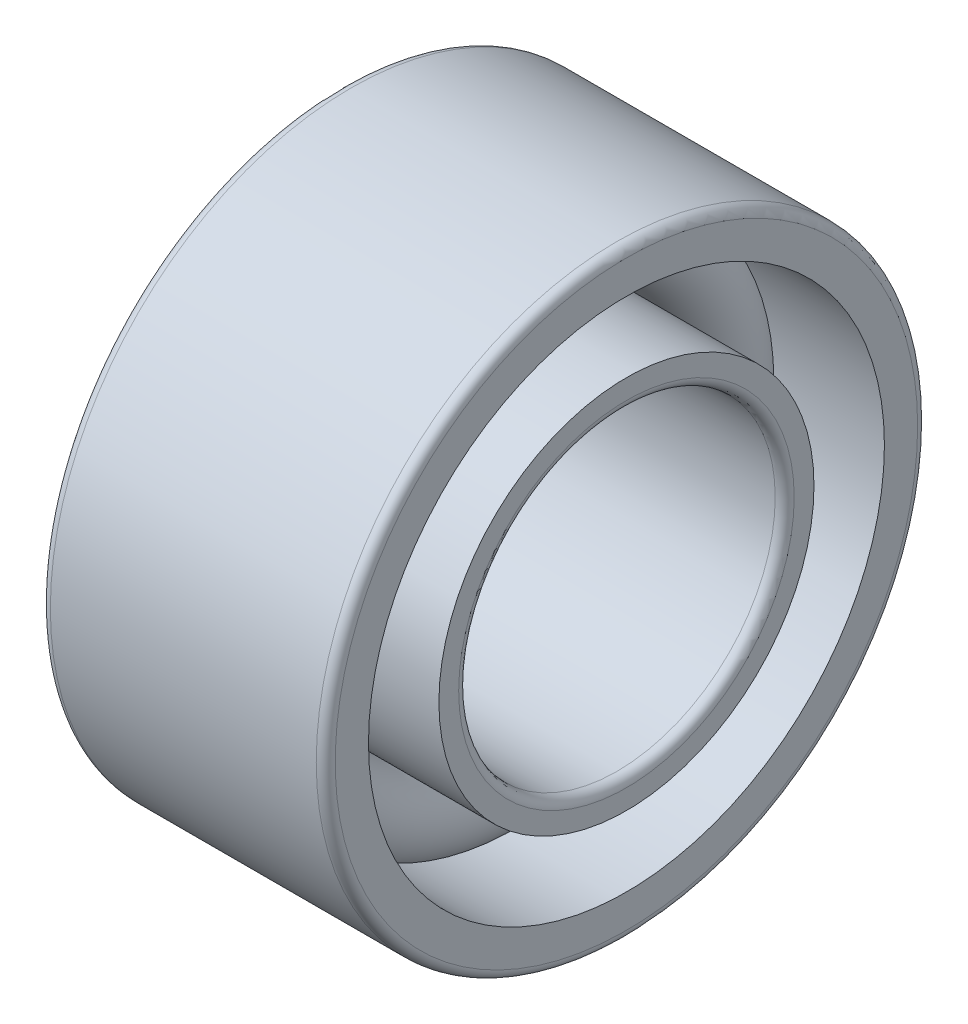
SolidWorks part; units mm, degrees
ref_plane "Plane1" through (0, 0, 0) normal (0, 0, 1) x (1, 0, 0)
ref_plane "Plane2" through (0, 0, 0) normal (0, 1, 0) x (1, 0, 0)
ref_plane "Plane3" through (0, 0, 0) normal (1, 0, 0) x (0, 0, -1)
other "Configuration Table"
sketch "Clipboard" plane through (0, 0, 0) normal (0, 0, 1) x (1, 0, 0)
  line L0 (-10, 0) -> (10, 0) construction
  line L1 (0, 0) -> (22.3471, -0.7804)
  line L2 (0, 0) -> (7.2456, 0.253)
  line L3 (0, 0) -> (22.3471, -0.7804)
  line L4 (0, 0) -> (-22.3573, -0.3902)
  dimension "BallCLRad" = 7.25
sketch "CagSpiSke" plane through (0, 0, 0) normal (0, 0, 1) x (1, 0, 0)
  line L0 (0.3375, 7.025) -> (0.3375, 7.475)
  line L1 (0.3375, 7.475) -> (-0.3375, 7.475)
  line L2 (-0.3375, 7.475) -> (-0.3375, 7.025)
  line L3 (-0.3375, 7.025) -> (0.3375, 7.025)
  line L4 (-20.6375, 0) -> (20.6375, 0) construction
  line L5 (0, 0) -> (0, 23.7692) construction
  dimension "OD" = 14.95
  dimension "ID" = 14.05
revolve "CageSpine" add sketch "CagSpiSke" angle 0.001 about L4
ref_axis "Axis1" through (-50, 0, 0) along (1, 0, 0)
sketch "CagBalSke" plane through (0, 0, 0) normal (0, 0, 1) x (1, 0, 0)
  line L0 (-1.485, 7.25) -> (1.485, 7.25)
  line L1 (-1.905, 7.25) -> (1.905, 7.25) construction
  line L2 (-10, 0) -> (10, 0) construction
  line L3 (0, 0) -> (0, 24) construction
  arc A0 (1.485, 7.25) -> (-1.485, 7.25) centre (0, 7.25) cw
  dimension "BallCLRad" = 7.25
revolve "CageBall" [suppressed] add sketch "CagBalSke" angle 360 about L1 reverse direction yes
pattern_circular "CageBalls" [suppressed] count 2 every 180 about axis through (-50, 0, 0) along (1, 0, 0)
sketch "CagTrmODSke" plane through (0, 0, 0) normal (0, 0, 1) x (1, 0, 0)
  line L0 (1.486, 7.475) -> (1.486, 8.736)
  line L1 (1.486, 8.736) -> (-1.486, 8.736)
  line L2 (-1.486, 8.736) -> (-1.486, 7.475)
  line L3 (-1.486, 7.475) -> (1.486, 7.475)
  line L4 (-20.6375, 0) -> (20.6375, 0) construction
  line L5 (0, 0) -> (0, 25) construction
  dimension "Width" = 2.972
  dimension "ID" = 14.95
  dimension "OD" = 17.472
revolve "CageTrimOD" [suppressed] cut sketch "CagTrmODSke" angle 360 about L4 reverse direction yes
sketch "CagTrmIDSke" plane through (0, 0, 0) normal (0, 0, 1) x (1, 0, 0)
  line L0 (1.486, 5.766) -> (1.486, 7.025)
  line L1 (1.486, 7.025) -> (-1.486, 7.025)
  line L2 (-1.486, 7.025) -> (-1.486, 5.766)
  line L3 (-1.486, 5.766) -> (1.486, 5.766)
  line L4 (-20.6375, 0) -> (20.6375, 0) construction
  line L5 (0, 0) -> (0, 25) construction
  dimension "Width" = 2.972
  dimension "ID" = 11.532
  dimension "OD" = 14.05
revolve "CageTrimID" [suppressed] cut sketch "CagTrmIDSke" angle 360 about L4 reverse direction yes
sketch "BalSimSke" plane through (0, 0, 0) normal (0, 0, 1) x (1, 0, 0)
  line L0 (-10, 0) -> (10, 0) construction
  line L1 (-10, 7.25) -> (10, 7.25) construction
  line L2 (0, 0) -> (0, 23) construction
  circle A0 centre (0, 7.25) radius 1.35
  dimension "BallCLRad" = 7.25
  dimension "Ball_diameter" = 2.7
revolve "BallsSimplified" add sketch "BalSimSke" angle 360 about L0
sketch "BalDetSke" plane through (0, 0, 0) normal (0, 0, 1) x (1, 0, 0)
  line L0 (-1.35, 7.25) -> (1.35, 7.25)
  line L1 (-1.905, 7.25) -> (1.905, 7.25) construction
  line L2 (0, 0) -> (0, 25) construction
  arc A0 (1.35, 7.25) -> (-1.35, 7.25) centre (0, 7.25) cw
  dimension "BallCLRad" = 7.25
  dimension "Ball_diameter" = 2.7
revolve "BallDetailed" [suppressed] add sketch "BalDetSke" angle 360 about L1 reverse direction yes
sketch "InnRacSke" plane through (0, 0, 0) normal (0, 0, 1) x (1, 0, 0)
  line L0 (-0.9724, 6.35) -> (-4.5, 6.35)
  line L1 (-4.5, 6.35) -> (-4.5, 5.3)
  line L2 (-4.2, 5) -> (4.2, 5)
  line L3 (4.5, 5.3) -> (4.5, 5.925)
  line L4 (0, 5.925) -> (4.5, 5.925)
  line L5 (-20.6375, 0) -> (20.6375, 0) construction
  line L6 (0, 0) -> (0, 30) construction
  arc A0 (-4.5, 5.3) -> (-4.2, 5) centre (-4.2, 5.3) ccw
  arc A1 (4.2, 5) -> (4.5, 5.3) centre (4.2, 5.3) ccw
  arc A2 (0, 5.925) -> (-0.9724, 6.35) centre (0, 7.25) cw
  dimension "BallCLRad" = 7.25
  dimension "Fillet_radius" = 0.3
  dimension "Ball_diameter" = 2.65
  dimension "ID" = 10
  dimension "OD" = 12.7
  dimension "Width" = 9
revolve "InnerRace" add sketch "InnRacSke" angle 360 about L5 reverse direction yes
sketch "OutRacSke" plane through (0, 0, 0) normal (0, 0, 1) x (1, 0, 0)
  line L0 (0, 8.575) -> (-4.5, 8.575)
  line L1 (-4.5, 8.575) -> (-4.5, 9.2)
  line L2 (-4.2, 9.5) -> (4.2, 9.5)
  line L3 (4.5, 9.2) -> (4.5, 8.15)
  line L4 (4.5, 8.15) -> (0.9724, 8.15)
  line L5 (-20.6375, 0) -> (20.6375, 0) construction
  line L6 (0, 0) -> (0, 30) construction
  arc A0 (-4.5, 9.2) -> (-4.2, 9.5) centre (-4.2, 9.2) cw
  arc A1 (4.2, 9.5) -> (4.5, 9.2) centre (4.2, 9.2) cw
  arc A2 (0.9724, 8.15) -> (0, 8.575) centre (0, 7.25) ccw
  dimension "BallCLRad" = 7.25
  dimension "Fillet_radius" = 0.3
  dimension "Ball_diameter" = 2.65
  dimension "Width" = 9
revolve "OuterRace" add sketch "OutRacSke" angle 360 about L5 reverse direction yes
pattern_circular "BallsDetailed" [suppressed] count 2 every 180 about axis through (-50, 0, 0) along (1, 0, 0)
equation "\"BallCLRad@Clipboard\" = ( \"OD@OutRacSke\" + \"ID@InnRacSke\" ) / 4"
equation "\"BallCLRad@BalSimSke\" = \"BallCLRad@Clipboard\""
equation "\"BallCLRad@BalDetSke\" = \"BallCLRad@Clipboard\""
equation "\"BallCLRad@InnRacSke\" = \"BallCLRad@Clipboard\""
equation "\"BallCLRad@OutRacSke\" = \"BallCLRad@Clipboard\""
equation "\"Ball_diameter@InnRacSke\" = \"Ball_diameter@BalDetSke\" - 0.05"
equation "\"Ball_diameter@OutRacSke\" = \"Ball_diameter@BalDetSke\" - 0.05"
equation "\"Ball_diameter@BalSimSke\" = \"Ball_diameter@BalDetSke\""
equation "\"Width@OutRacSke\" = \"Width@InnRacSke\""
equation "\"Fillet_radius@OutRacSke\" = \"Fillet_radius@InnRacSke\""
equation "\"Max_count@Clipboard\" = int( 3.14159265 / atn(( \"Ball_diameter@BalDetSke\" / 2) / sqr( \"BallCLRad@Clipboard\"  *  \"BallCLRad@Clipboard\" - ( \"Ball_diameter@BalDetSke\" / 2) *  ( \"Ball_diameter@BalDetSke\" / 2))))"
equation "\"Max_count@Clipboard\" = ((sgn( \"Max_count@Clipboard\" - \"Count@Clipboard\" )-1)*( \"Max_count@Clipboard\" - \"Count@Clipboard\" ))/-2+ \"Count@Clipboard\""
equation "\"Count@BallsDetailed\" = int( \"Show_count@Clipboard\" ) "
equation "\"Count@BallsDetailed\" = ((sgn( \"Count@BallsDetailed\" - \"Max_count@Clipboard\" )-1)*( \"Count@BallsDetailed\" - \"Max_count@Clipboard\" ))/-2+ \"Max_count@Clipboard\""
equation "\"Count@BallsDetailed\" = ((sgn( \"Count@BallsDetailed\" - \"Min_count@Clipboard\" )+1)*( \"Count@BallsDetailed\" - \"Min_count@Clipboard\"))/2 +\"Min_count@Clipboard\""
equation "\"Angle@BallsDetailed\" = 360.0 / \"Max_count@Clipboard\""
equation "\"BallCLRad@CagBalSke\" = \"BallCLRad@Clipboard\""
equation "\"Count@CageBalls\" = \"Count@BallsDetailed\""
equation "\"Angle@CageBalls\" = \"Angle@BallsDetailed\""
equation "\"Angle@CageSpine\" =  \"Angle@CageBalls\" * ( \"Count@CageBalls\" -1 + int( \"Count@CageBalls\" / \"Max_count@Clipboard\" ) )  + 0.001 -  int( \"Count@CageBalls\" / \"Max_count@Clipboard\" ) * 0.001"
equation "\"Angle@CageSpine\" =  \"Angle@CageSpine\" * int( \"Min_count@Clipboard\" / 2) + int(1 / \"Min_count@Clipboard\")  * 0.001"
equation "\"CageWallOD@CagBalSke\" =  \"Ball_diameter@BalDetSke\" * 1.1"
equation "\"Thickness@CagSpiSke\" =  \"Ball_diameter@BalDetSke\" * 0.25"
equation "\"OD@CagTrmODSke\" = \"BallCLRad@Clipboard\" * 2 + \"CageWallOD@CagBalSke\" + 0.002"
equation "\"ID@CagTrmODSke\" = \"BallCLRad@Clipboard\" * 2 + \"Ball_diameter@BalDetSke\" / 6"
equation "\"OD@CagTrmIDSke\" = \"BallCLRad@Clipboard\" * 2 - \"Ball_diameter@BalDetSke\" / 6"
equation "\"ID@CagTrmIDSke\" = \"BallCLRad@Clipboard\" * 2 - \"CageWallOD@CagBalSke\" + 0.002"
equation "\"OD@CagSpiSke\" = \"ID@CagTrmODSke\""
equation "\"ID@CagSpiSke\" = \"OD@CagTrmIDSke\""
equation "\"Width@CagTrmODSke\" = \"CageWallOD@CagBalSke\" + 0.002"
equation "\"Width@CagTrmIDSke\" = \"CageWallOD@CagBalSke\" + 0.002"
